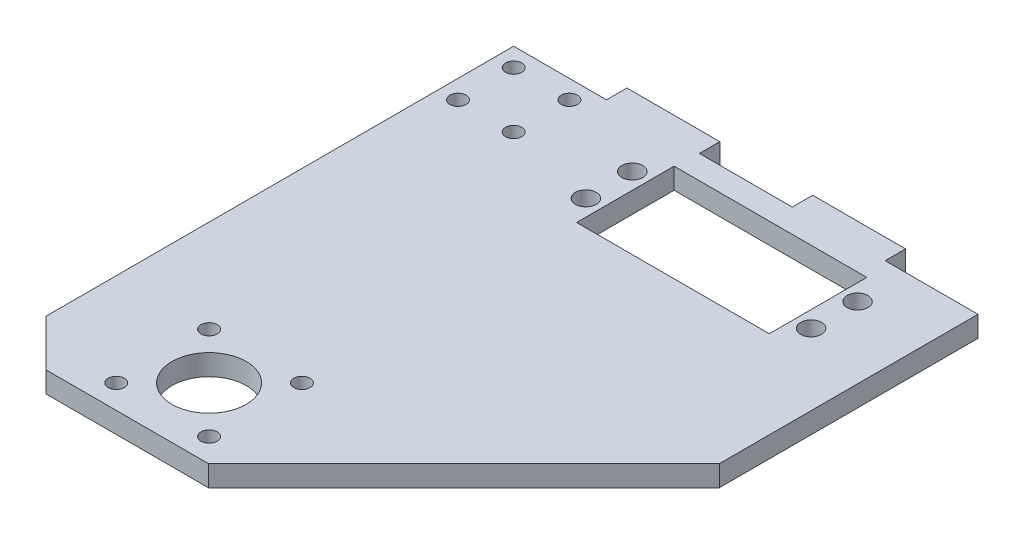
SolidWorks part; units mm, degrees
ref_plane "Front Plane" through (0, 0, 0) normal (0, 0, 1) x (1, 0, 0)
ref_plane "Top Plane" through (0, 0, 0) normal (0, 1, 0) x (1, 0, 0)
ref_plane "Right Plane" through (0, 0, 0) normal (1, 0, 0) x (0, 0, -1)
sketch "Sketch2" plane through (0, 0, 0) normal (0, 1, 0) x (1, 0, 0)
  line L3 (110, 70) -> (-110, 70)
  line L4 (110, 70) -> (110, -70)
  line L5 (110, -70) -> (-110, -70)
  line L6 (-110, 70) -> (-110, -70)
  line L7 (110, 70) -> (-110, -70) construction
  line L8 (110, -70) -> (-110, 70) construction
  point P0 (0, 0)
  dimension "D1" = 220
  dimension "D2" = 140
extrude "Boss-Extrude1" add sketch "Sketch2" along normal blind 4.5
chamfer "Chamfer1" [suppressed] distance 75 angle 40
sketch "Sketch3" plane through (0, 4.5, 0) normal (0, 1, 0) x (1, 0, 0)
  line L0 (0, 70) -> (0, -30) construction
  line L1 (110, 70) -> (-110, 70) construction
  line L2 (0, -30) -> (40.6, -30) construction
  line L3 (40.6, -30) -> (40.6, 50) construction
  circle A0 centre (0, -30) radius 8
  circle A1 centre (40.6, 50) radius 8
  point P9 (0, 0)
  dimension "D2" = 16
  dimension "D5" = 16
  dimension "D1" = 100
  dimension "D3" = 80
  dimension "D4" = 40.6
extrude "Cut-Extrude1" cut sketch "Sketch3" against normal through all
sketch "Sketch4" plane through (0, 0, 0) normal (0, -1, 0) x (1, 0, 0)
  line L0 (110, 70) -> (110, -70) construction
  line L1 (110, -70) -> (90, -70)
  line L2 (110, -70) -> (110, -65.6)
  line L3 (110, -65.6) -> (90, -65.6)
  line L4 (90, -70) -> (90, -65.6)
  line L5 (110, -70) -> (90, -65.6) construction
  line L6 (110, -65.6) -> (90, -70) construction
  line L7 (0, -70) -> (0, 0) construction
  line L8 (70, -70) -> (50, -70)
  line L9 (70, -70) -> (70, -65.6)
  line L10 (70, -65.6) -> (50, -65.6)
  line L11 (50, -70) -> (50, -65.6)
  line L12 (70, -70) -> (50, -65.6) construction
  line L13 (70, -65.6) -> (50, -70) construction
  line L14 (30, -70) -> (10, -70)
  line L15 (30, -70) -> (30, -65.6)
  line L16 (30, -65.6) -> (10, -65.6)
  line L17 (10, -70) -> (10, -65.6)
  line L18 (30, -70) -> (10, -65.6) construction
  line L19 (30, -65.6) -> (10, -70) construction
  line L20 (-30, -65.6) -> (-10, -70) construction
  line L21 (-30, -70) -> (-10, -65.6) construction
  line L22 (-70, -65.6) -> (-50, -70) construction
  line L23 (-70, -70) -> (-50, -65.6) construction
  line L24 (-110, -65.6) -> (-90, -70) construction
  line L25 (-110, -70) -> (-90, -65.6) construction
  line L26 (-10, -70) -> (-10, -65.6)
  line L27 (-30, -65.6) -> (-10, -65.6)
  line L28 (-30, -70) -> (-30, -65.6)
  line L29 (-30, -70) -> (-10, -70)
  line L30 (-50, -70) -> (-50, -65.6)
  line L31 (-70, -65.6) -> (-50, -65.6)
  line L32 (-70, -70) -> (-70, -65.6)
  line L33 (-70, -70) -> (-50, -70)
  line L34 (-90, -70) -> (-90, -65.6)
  line L35 (-110, -65.6) -> (-90, -65.6)
  line L36 (-110, -70) -> (-110, -65.6)
  line L37 (-110, -70) -> (-90, -70)
  line L38 (0, -70) -> (110, -70) construction
  point P4 (100, -67.8)
  point P29 (-100, -67.8)
  dimension "D1" = 4.4
  dimension "D2" = 20
  dimension "D3" = 3
  dimension "D4" = 70
  dimension "D5" = 20
extrude "Teeth cut" cut sketch "Sketch4" against normal through all
sketch "Sketch5" plane through (0, 0, 0) normal (0, -1, 0) x (1, 0, 0)
  line L0 (-110, 70) -> (110, 70) construction
  line L1 (110, -70.1) -> (70, -70.1)
  line L2 (110, -70.1) -> (110, 70)
  line L3 (110, 70) -> (70, 70)
  line L4 (70, -70.1) -> (70, 45.1242)
  line L5 (110, -70.1) -> (70, 70) construction
  line L6 (110, 70) -> (70, -70.1) construction
  line L7 (-110, -65.6) -> (-110, 70) construction
  line L8 (-30, -70.1) -> (-110, -70.1)
  line L9 (-30, -70.1) -> (-30, 45.1242)
  line L10 (-30, 70) -> (-110, 70)
  line L11 (-110, -70.1) -> (-110, 70)
  line L12 (-30, -70.1) -> (-110, 70) construction
  line L13 (-30, 70) -> (-110, -70.1) construction
  line L14 (110, 70) -> (110, -65.6) construction
  line L15 (-30, 45.1242) -> (-30, 70) construction
  line L16 (-30, 70) -> (70, 70)
  line L17 (-30, 70) -> (-30, 45.1242) construction
  line L18 (-30, 45.1242) -> (70, 45.1242)
  line L19 (70, 70) -> (70, 45.1242) construction
  line L20 (70, 45.1242) -> (70, 70) construction
  point P4 (90, -0.05)
  point P11 (-70, -0.05)
  dimension "D1" = 80
  dimension "D2" = 40
extrude "Trim cut" cut sketch "Sketch5" against normal through all
sketch "Sketch6" plane through (0, 4.5, 0) normal (0, 1, 0) x (1, 0, 0)
  line L0 (-30, 65.6) -> (-30, -45.1242) construction
  line L1 (51.15, 39.5) -> (9.65, 39.5)
  line L2 (51.15, 39.5) -> (51.15, 60.5)
  line L3 (51.15, 60.5) -> (9.65, 60.5)
  line L4 (9.65, 39.5) -> (9.65, 60.5)
  line L5 (51.15, 39.5) -> (9.65, 60.5) construction
  line L6 (51.15, 60.5) -> (9.65, 39.5) construction
  line L7 (-10, 65.6) -> (-30, 65.6) construction
  line L8 (-10, 65.6) -> (-10, 45.6) construction
  line L9 (-10, 45.6) -> (-30, 45.6) construction
  line L10 (-30, 65.6) -> (-30, 45.6) construction
  line L11 (-14, 61.6) -> (-26, 61.6) construction
  line L12 (-26, 61.6) -> (-26, 49.6) construction
  line L13 (-14, 49.6) -> (-26, 49.6) construction
  line L14 (-14, 61.6) -> (-14, 49.6) construction
  circle A0 centre (6.15, 55) radius 2.25
  circle A1 centre (6.15, 45) radius 2.25
  circle A2 centre (54.65, 45) radius 2.25
  circle A3 centre (54.65, 55) radius 2.25
  circle A4 centre (-14, 49.6) radius 1.75
  circle A5 centre (10, -20) radius 1.75
  circle A6 centre (10, -40) radius 1.75
  circle A7 centre (-10, -40) radius 1.75
  circle A8 centre (-10, -20) radius 1.75
  circle A9 centre (-26, 49.6) radius 1.75
  circle A10 centre (-26, 61.6) radius 1.75
  circle A11 centre (-14, 61.6) radius 1.75
  point P24 (30.4, 50)
  dimension "D1" = 4.5
  dimension "D2" = 3.5
  dimension "D3" = 21
  dimension "D4" = 41.5
  dimension "D5" = 20
  dimension "D6" = 4
extrude "Cut-Extrude2" cut sketch "Sketch6" against normal through all
ref_axis "Axis1" through (40.6, 42.5401, -50) along (0, -1, 0)
chamfer "Chamfer4" distance 10 angle 45 1 edges at (-30, 2.25, 45.1242)
chamfer "Chamfer5" distance 55 angle 45 1 edges at (70, 2.25, 45.1242)
